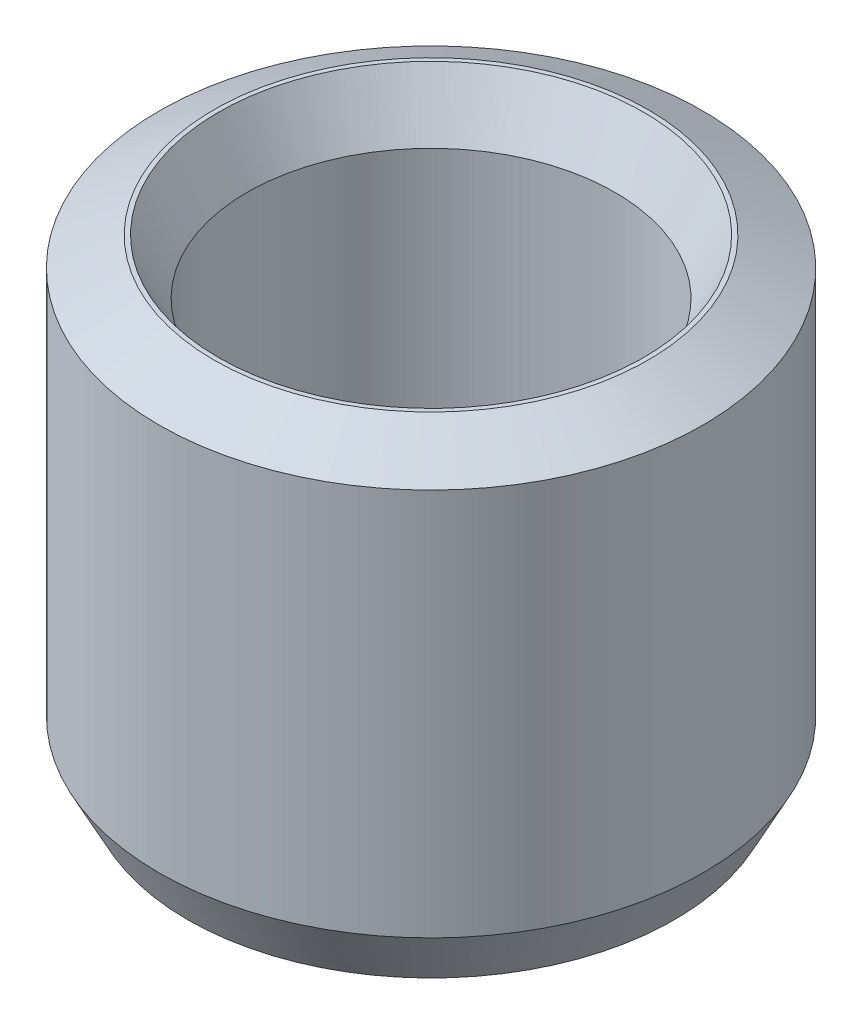
SolidWorks part; units mm, degrees
ref_plane "Front Plane" through (0, 0, 0) normal (0, 0, 1) x (1, 0, 0)
ref_plane "Top Plane" through (0, 0, 0) normal (0, 1, 0) x (1, 0, 0)
ref_plane "Right Plane" through (0, 0, 0) normal (1, 0, 0) x (0, 0, -1)
sketch "Sketch1" plane through (0, 0, 0) normal (0, 1, 0) x (1, 0, 0)
  circle A0 centre (0, 0) radius 20
  dimension "SLEEVE_OD" = 40
extrude "Boss-Extrude1" add sketch "Sketch1" along normal blind 34.6714
sketch "Sketch2" plane through (0, 0, 0) normal (0, 1, 0) x (1, 0, 0)
  circle A0 centre (0, 0) radius 13.5181
  dimension "BORE_D" = 27.0363
extrude "Cut-Extrude1" cut sketch "Sketch2" along normal through all
chamfer "Chamfer1" distance 2.1106 angle 62.446 4 edges at (0, 34.6714, 13.5181) (0, 0, 13.5181) (0, 0, 20) (0, 34.6714, 20) first distance on face at (0, 34.6714, 13.5181) first distance on face at (0, 0, 13.5181) first distance on face at (0, 34.6714, 20)
